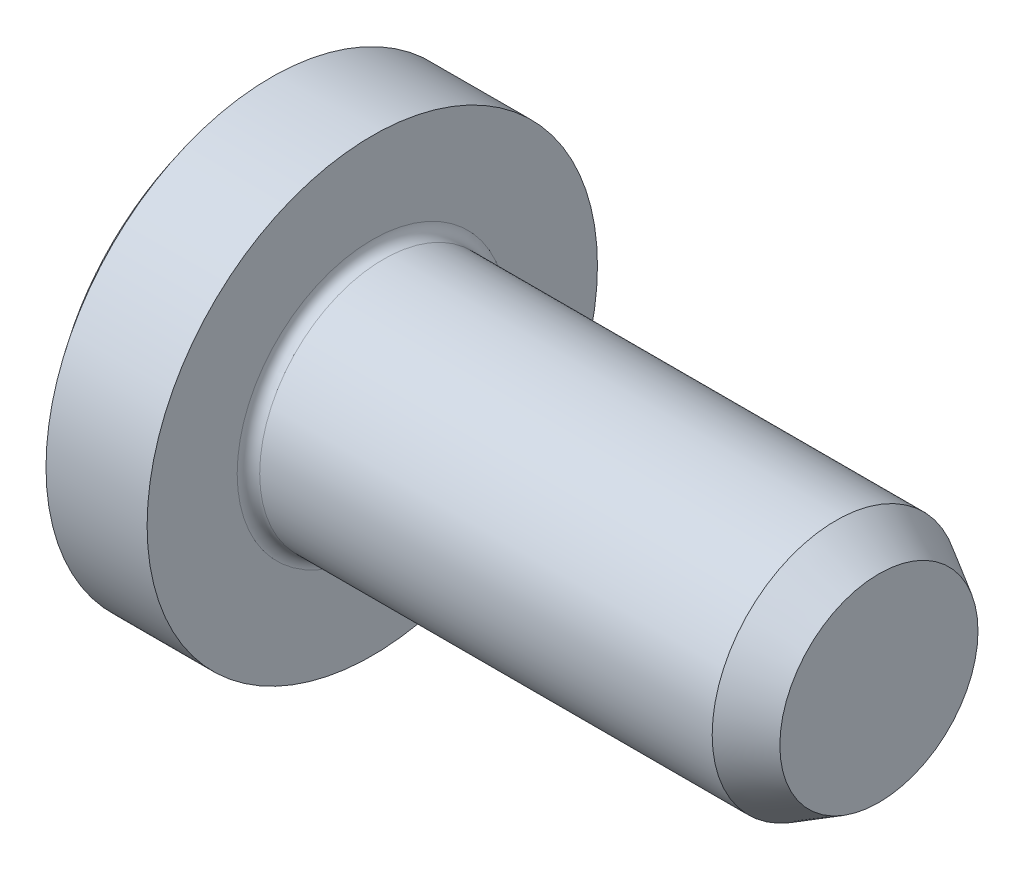
SolidWorks part; units mm, degrees
ref_plane "Front Plane" through (0, 0, 0) normal (0, 0, 1) x (1, 0, 0)
ref_plane "Top Plane" through (0, 0, 0) normal (0, 1, 0) x (1, 0, 0)
ref_plane "Right Plane" through (0, 0, 0) normal (1, 0, 0) x (0, 0, -1)
sketch "Sketch1" plane through (0, 0, 0) normal (0, 0, 1) x (1, 0, 0)
  line L0 (0, 0) -> (5.2282, 0) construction
  line L2 (0, 2) -> (-0.898, 2)
  line L3 (-1.6, 0) -> (-1.6, -0.7496) construction
  line L4 (-1.6, 0) -> (4.5, 0)
  line L5 (0, 1.1) -> (4.5, 1.1)
  line L6 (4.5, 1.1) -> (4.5, 0)
  line L7 (0, 1.1) -> (0, 2)
  arc A0 (-0.898, 2) -> (-1.6, 0) centre (1.6, 0) ccw
  dimension "l" = 4.5
revolve "Revolve1" add sketch "Sketch1" angle 360 about L0
cosmetic thread "ThreadCosmetic" [suppressed] parameters "D1"=4.28, "D2"=1.65
chamfer "Chamfer1" distance 0.22 angle 60 1 edges at (4.5, 0, 1.1) first distance on face at (4.5, 0, 1.1)
sketch "Sketch5" plane through (0, 0, 0) normal (0, 0, 1) x (1, 0, 0)
  line L0 (0.3703, 0.825) -> (0.2069, 0.825)
  line L1 (0.2069, 0.825) -> (0.0481, 1.1)
  line L2 (0.3703, 0.825) -> (0.529, 1.1)
  line L3 (0.0481, 1.1) -> (0.0481, 1.35)
  line L4 (0.529, 1.1) -> (0.529, 1.35)
  line L5 (0.0481, 1.35) -> (0.529, 1.35)
  line L6 (0.2886, 0.825) -> (0.2886, 0) construction
  line L7 (0, 0) -> (7.3035, 0) construction
  line L9 (4.1189, 1.1) -> (0, 1.1) construction
  line L12 (0, -1.1) -> (0, 1.1) construction
  dimension "D2" = 60
  dimension "D3" = 0.25
  dimension "minordia" = 1.65
  dimension "threadstart" = 0.2886
revolve "ThreadSchematic" [suppressed] cut sketch "Sketch5" angle 360 about L7
pattern_linear "ThdSchPat" [suppressed] count 10 spacing 0.4809 along (1, 0, 0) of bodies 105
sketch "Sketch2" plane through (0, 0, 0) normal (0, 0, 1) x (1, 0, 0)
  line L0 (0, 0) -> (5.7679, 0) construction
  line L1 (4.5, 0) -> (2.5947, 1.1)
  line L3 (4.5, 1.1) -> (4.5, 0) construction
  line L4 (2.5947, 1.1) -> (2.5947, 1.2)
  line L5 (2.5947, 1.2) -> (4.6, 1.2)
  line L6 (4.6, 1.2) -> (4.6, 0)
  line L7 (4.6, 0) -> (4.5, 0)
  point P9 (0, 1.1)
  dimension "D1" = 30
  dimension "D2" = 0.1
  dimension "D3" = 0.1
revolve "EndCone" [suppressed] cut sketch "Sketch2" angle 360 about L0
ref_plane "Plane4" through (-1.6, 0, 0) normal (1, 0, 0) x (0, 0, -1)
sketch "Sketch3" plane through (-1.6, 0, 0) normal (1, 0, 0) x (0, 0, -1)
  line L0 (0, 2.343) -> (0, -2.4842) construction
  line L1 (2.7661, 0) -> (-3.4558, 0) construction
  line L2 (-0.2375, 0.95) -> (0.2375, 0.95)
  line L3 (0.2375, 0.95) -> (0.1425, 0.57)
  line L4 (0, 0) -> (1.9578, 1.9578) construction
  line L5 (0.1425, 0.57) -> (0.299, 0.299)
  line L6 (0.1425, 0.57) -> (0, 0) construction
  line L7 (-0.1425, 0.57) -> (-0.299, 0.299)
  line L8 (-0.2375, 0.95) -> (-0.1425, 0.57)
  line L9 (0.95, 0.2375) -> (0.95, -0.2375)
  line L10 (0.95, -0.2375) -> (0.57, -0.1425)
  line L11 (0.57, -0.1425) -> (0.299, -0.299)
  line L12 (0.57, 0.1425) -> (0.299, 0.299)
  line L13 (0.95, 0.2375) -> (0.57, 0.1425)
  line L14 (0.2375, -0.95) -> (-0.2375, -0.95)
  line L15 (-0.2375, -0.95) -> (-0.1425, -0.57)
  line L16 (-0.1425, -0.57) -> (-0.299, -0.299)
  line L17 (0.1425, -0.57) -> (0.299, -0.299)
  line L18 (0.2375, -0.95) -> (0.1425, -0.57)
  line L19 (-0.95, -0.2375) -> (-0.95, 0.2375)
  line L20 (-0.95, 0.2375) -> (-0.57, 0.1425)
  line L21 (-0.57, 0.1425) -> (-0.299, 0.299)
  line L22 (-0.57, -0.1425) -> (-0.299, -0.299)
  line L23 (-0.95, -0.2375) -> (-0.57, -0.1425)
  point P14 (0, 0.95)
  point P23 (0.95, 0)
  point P30 (0, -0.95)
  point P37 (-0.95, 0)
  dimension "D1" = 45
  dimension "D3" = 0.475
  dimension "D4" = 75
  dimension "D5" = 1.14
  dimension "m" = 1.9
extrude "Cut-Extrude1" cut sketch "Sketch3" along normal blind 0.8 draft 6
sketch "Sketch4" plane through (-1.6, 0, 0) normal (1, 0, 0) x (0, 0, -1)
  line L0 (0, 2.1951) -> (0, -2.1951) construction
  line L1 (2.1996, 0) -> (-2.3835, 0) construction
  line L2 (-0.8397, -0.8397) -> (0.8397, 0.8397) construction
  line L3 (0.95, 0.2375) -> (-0.95, 0.2375)
  line L4 (0.95, 0.2375) -> (0.95, -0.2375)
  line L5 (0.95, -0.2375) -> (-0.95, -0.2375)
  line L6 (-0.95, 0.2375) -> (-0.95, -0.2375)
  line L7 (0.2375, 0.95) -> (-0.2375, 0.95)
  line L8 (0.2375, 0.95) -> (0.2375, -0.95)
  line L9 (0.2375, -0.95) -> (-0.2375, -0.95)
  line L10 (-0.2375, 0.95) -> (-0.2375, -0.95)
  line L11 (0.8397, 0.8397) -> (0.3859, 0.2375)
  line L12 (0.8397, 0.8397) -> (0.2375, 0.3859)
  line L13 (0.2375, 0.3859) -> (-0.2375, 0.3859) construction
  line L14 (0, 0) -> (-0.8397, 0.8397) construction
  line L15 (-0.8397, -0.8397) -> (-0.2375, -0.3859)
  line L16 (-0.8397, -0.8397) -> (-0.3859, -0.2375)
  line L17 (-0.2375, 0.3859) -> (-0.8397, 0.8397)
  line L18 (-0.8397, 0.8397) -> (-0.3859, 0.2375)
  line L19 (-0.3859, -0.2375) -> (-0.3859, 0.2375) construction
  line L20 (0.3859, -0.2375) -> (0.8397, -0.8397)
  line L21 (0.8397, -0.8397) -> (0.2375, -0.3859)
  circle A0 centre (0, 0) radius 1.1875 construction
  dimension "D1" = 2.375
  dimension "D2" = 0.475
  dimension "m" = 1.9
  dimension "D3" = 45
  dimension "D4" = 8
  dimension "D5" = 45
extrude "TypeZ" [suppressed] cut sketch "Sketch4" along normal blind 0.8
fillet "Fillet1" radius 0.1 1 edges at (0, 0, 1.1)
equation "\"D1@Chamfer1\" = \"d@Sketch1\"/10"
equation "\"D1@ThreadCosmetic\" = \"l@Sketch1\" - \"D1@Chamfer1\""
equation "\"minordia@Sketch5\" = \"D2@ThreadCosmetic\""
equation "\"D1@Plane4\" = \"K@Sketch1\""
equation "\"D5@Sketch3\" = \"m@Sketch3\" * 3 / 5"
equation "\"D3@Sketch3\" = \"m@Sketch3\" / 4"
equation "\"m@Sketch4\" = \"m@Sketch3\""
equation "\"D2@Sketch4\" =  \"m@Sketch4\" / 4"
equation "\"D1@TypeZ\" = \"K@Sketch1\" / 2"
equation "\"D1@Sketch4\" = \"m@Sketch4\" * 5 / 4"
equation "\"threadstart@Sketch5\" = \"advance@Sketch5\"*0.6"
equation "\"D1@ThdSchPat\" = int((\"l@Sketch1\"/\"advance@Sketch5\") + 0.8)"
equation "\"D3@ThdSchPat\" = \"advance@Sketch5\""
